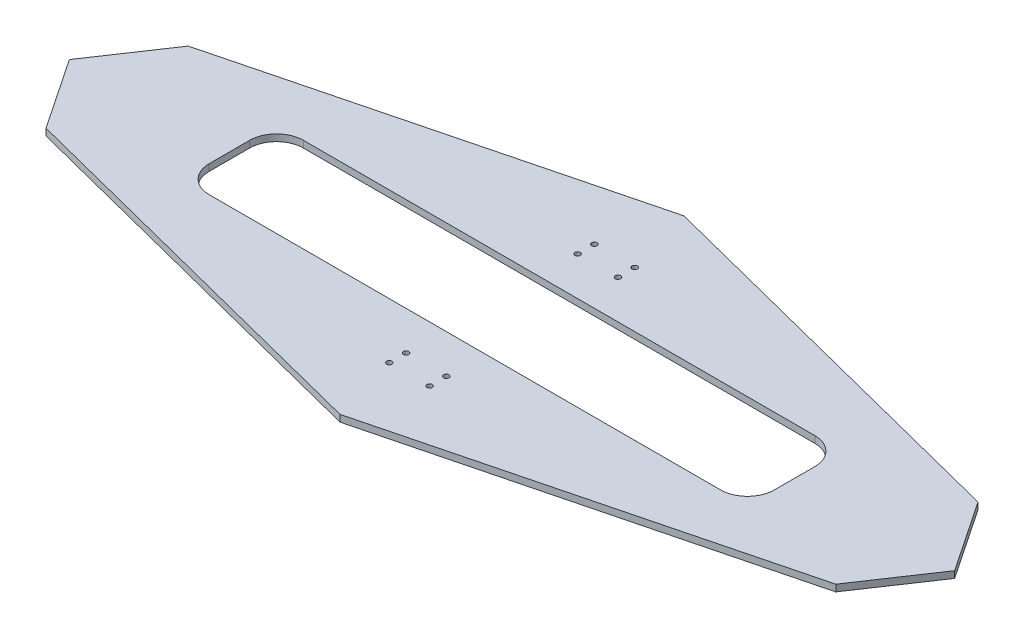
SolidWorks part; units mm, degrees
material "AISI 1020"
ref_plane "Front Plane" through (0, 0, 0) normal (0, 0, 1) x (1, 0, 0)
ref_plane "Top Plane" through (0, 0, 0) normal (0, 1, 0) x (1, 0, 0)
ref_plane "Right Plane" through (0, 0, 0) normal (1, 0, 0) x (0, 0, -1)
sketch "Sketch1" plane through (0, 0, 0) normal (0, 1, 0) x (1, 0, 0)
  line L0 (0, 0) -> (0, 457.2) construction
  line L1 (-762, 0) -> (-549.0794, 317.0112) construction
  line L2 (-762, 0) -> (0, 0) construction
  line L3 (549.0794, -317.0112) -> (-549.0794, -317.0112) construction
  line L4 (549.0794, -317.0112) -> (549.0794, 317.0112) construction
  line L5 (549.0794, 317.0112) -> (-549.0794, 317.0112) construction
  line L6 (-549.0794, -317.0112) -> (-549.0794, 317.0112) construction
  line L7 (549.0794, -317.0112) -> (-549.0794, 317.0112) construction
  line L8 (549.0794, 317.0112) -> (-549.0794, -317.0112) construction
  line L9 (-549.0794, 317.0112) -> (0, 457.2) construction
  line L10 (0, 457.2) -> (549.0794, 317.0112) construction
  line L11 (549.0794, 317.0112) -> (762, 0) construction
  line L12 (762, 0) -> (549.0794, -317.0112) construction
  line L13 (549.0794, -317.0112) -> (0, -457.2) construction
  line L14 (0, -457.2) -> (-549.0794, -317.0112) construction
  line L15 (-762, 0) -> (-549.0794, -317.0112) construction
  line L16 (-372.6919, 67.1293) -> (0, 162.2835)
  line L17 (0, 162.2835) -> (372.6919, 67.1293)
  line L18 (372.6919, 67.1293) -> (417.7793, 0)
  line L19 (417.7793, 0) -> (372.6919, -67.1293)
  line L20 (372.6919, -67.1293) -> (0, -162.2835)
  line L21 (0, -162.2835) -> (-372.6919, -67.1293)
  line L22 (-417.7793, 0) -> (-372.6919, -67.1293)
  line L23 (-417.7793, 0) -> (-372.6919, 67.1293)
  ellipse E0 centre (0, 0) end of major axis (-762, 0) minor radius 457.2 construction
  point P0 (0, 0)
  dimension "D1" = 762
  dimension "D2" = 457.2
  dimension "D3" = 30
  dimension "D4" = 285.75
extrude "Boss-Extrude1" add sketch "Sketch1" along normal mid plane 6.35
sketch "Sketch2" plane through (0, 0, 0) normal (0, 1, 0) x (1, 0, 0)
  line L0 (-266.7, 0) -> (0, 0) construction
  line L1 (241.3, 44.45) -> (-241.3, 44.45)
  line L2 (266.7, 19.05) -> (266.7, -19.05)
  line L3 (241.3, -44.45) -> (-241.3, -44.45)
  line L4 (-266.7, 19.05) -> (-266.7, -19.05)
  line L5 (266.7, 44.45) -> (-266.7, -44.45) construction
  line L6 (266.7, -44.45) -> (-266.7, 44.45) construction
  line L7 (-19.05, 96.8375) -> (19.05, 96.8375) construction
  line L8 (-19.05, 96.8375) -> (-19.05, 80.9625) construction
  line L9 (-19.05, 80.9625) -> (19.05, 80.9625) construction
  line L10 (19.05, 96.8375) -> (19.05, 80.9625) construction
  line L11 (-19.05, 96.8375) -> (19.05, 80.9625) construction
  line L12 (-19.05, 80.9625) -> (19.05, 96.8375) construction
  line L13 (0, 0) -> (0, 88.9) construction
  line L14 (-19.05, -80.9625) -> (19.05, -96.8375) construction
  line L15 (-19.05, -96.8375) -> (19.05, -80.9625) construction
  line L16 (19.05, -96.8375) -> (19.05, -80.9625) construction
  line L17 (-19.05, -80.9625) -> (19.05, -80.9625) construction
  line L18 (-19.05, -96.8375) -> (-19.05, -80.9625) construction
  line L19 (-19.05, -96.8375) -> (19.05, -96.8375) construction
  arc A0 (266.7, -19.05) -> (241.3, -44.45) centre (241.3, -19.05) cw
  arc A1 (241.3, 44.45) -> (266.7, 19.05) centre (241.3, 19.05) cw
  arc A2 (-241.3, -44.45) -> (-266.7, -19.05) centre (-241.3, -19.05) cw
  arc A3 (-241.3, 44.45) -> (-266.7, 19.05) centre (-241.3, 19.05) ccw
  circle A4 centre (19.05, 96.8375) radius 2.54
  circle A5 centre (-19.05, 96.8375) radius 2.54
  circle A6 centre (-19.05, 80.9625) radius 2.54
  circle A7 centre (19.05, 80.9625) radius 2.54
  circle A8 centre (19.05, -80.9625) radius 2.54
  circle A9 centre (-19.05, -80.9625) radius 2.54
  circle A10 centre (-19.05, -96.8375) radius 2.54
  circle A11 centre (19.05, -96.8375) radius 2.54
  point P0 (0, 0)
  point P18 (0, 88.9)
  point P38 (0, -88.9)
  dimension "D3" = 25.4
  dimension "D7" = 5.08
  dimension "D1" = 533.4
  dimension "D2" = 88.9
  dimension "D4" = 38.1
  dimension "D5" = 15.875
  dimension "D6" = 88.9
extrude "Cut-Extrude1" cut sketch "Sketch2" against normal through all both and the other way through all
